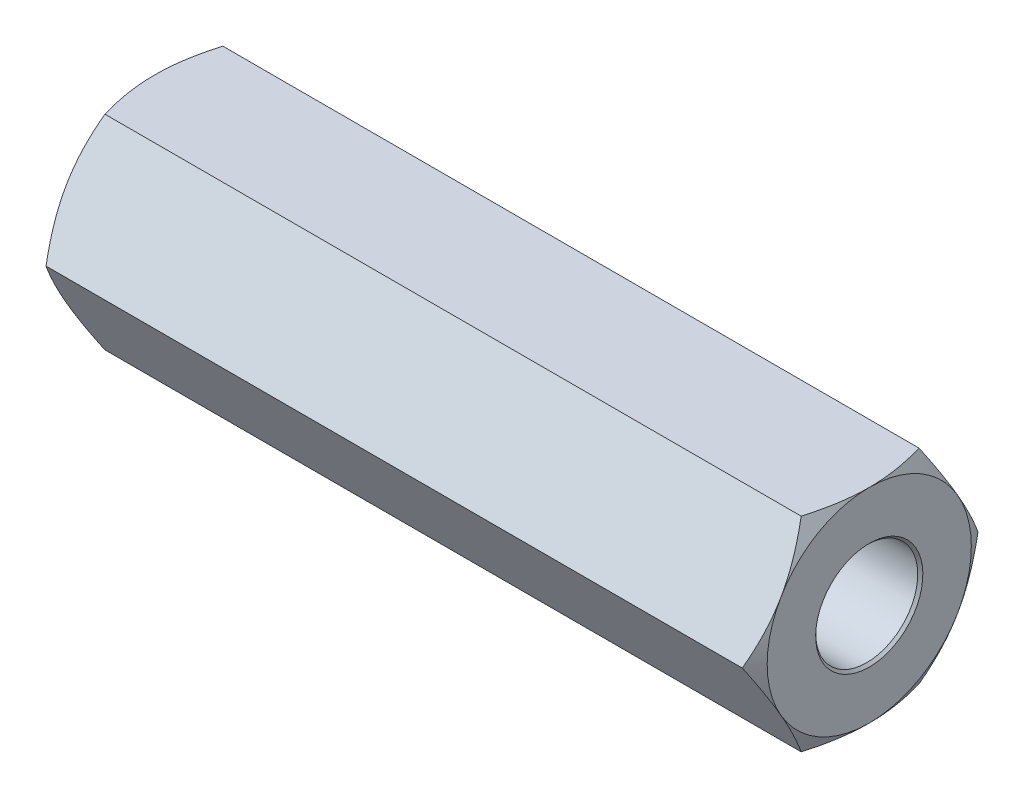
SolidWorks part; units mm, degrees
ref_plane "Front Plane" through (0, 0, 0) normal (0, 0, 1) x (1, 0, 0)
ref_plane "Top Plane" through (0, 0, 0) normal (0, 1, 0) x (1, 0, 0)
ref_plane "Right Plane" through (0, 0, 0) normal (1, 0, 0) x (0, 0, -1)
sketch "Sketch1" plane through (0, 0, 0) normal (0, 0, 1) x (1, 0, 0)
  line L0 (0, 0) -> (28, 0) construction
  line L1 (0, 4) -> (0, -4) construction
  line L2 (0, 2) -> (11.1, 2) construction
  line L3 (0, 2) -> (-0.7, 2) construction
  line L4 (0, 4) -> (28, 4) construction
  point P6 (0, 0)
  dimension "Hex" = 8
  dimension "Pitch" = 0.7
  dimension "Thread Length" = 11.1
  dimension "Thread OD" = 4
  dimension "Length" = 28
sketch "Sketch2" plane through (0, 0, 0) normal (1, 0, 0) x (0, 0, -1)
  line L0 (0, 0) -> (-1.4142, -1.4142) construction
  line L1 (2.3094, 4) -> (-2.3094, 4)
  line L2 (-2.3094, 4) -> (-4.6188, 0)
  line L3 (-4.6188, 0) -> (-2.3094, -4)
  line L4 (-2.3094, -4) -> (2.3094, -4)
  line L5 (2.3094, -4) -> (4.6188, 0)
  line L6 (4.6188, 0) -> (2.3094, 4)
  circle A0 centre (0, 0) radius 4 construction
  circle A1 centre (0, 0) radius 2 construction
  dimension "D1" = 45
extrude "Boss-Extrude1" add sketch "Sketch2" along normal up to vertex (28 mm away) up to point (28, 0, 0)
sketch "Sketch3" plane through (0, 0, 0) normal (0, 0, 1) x (1, 0, 0)
  line L0 (0, 2.1) -> (0.1, 2)
  line L1 (0, 0) -> (11.1, 0)
  line L2 (0, 0) -> (0, 2.1)
  line L3 (0.1, 2) -> (11.1, 2)
  line L4 (11.1, 0) -> (11.1, 2)
  line L5 (28, 0) -> (16.9, 0)
  line L8 (16.9, 0) -> (16.9, 2)
  line L9 (0, 4) -> (0, -4) construction
  line L13 (0, 0) -> (28, 0) construction
  line L14 (16.9, 2) -> (27.9, 2)
  line L15 (27.9, 2) -> (28, 2.1)
  line L16 (28, 4) -> (28, 0) construction
  line L17 (28, 2.1) -> (28, 0)
  dimension "D1" = 4.2
  dimension "D2" = 45
revolve "Cut-Revolve1" cut sketch "Sketch3" angle 360 about L13
sketch "Sketch4" plane through (0, 0, 0) normal (-1, 0, 0) x (0, 0, 1)
  circle A0 centre (0, 0) radius 4
  circle A1 centre (0, 0) radius 4 construction
extrude "Cut-Extrude1" cut sketch "Sketch4" against normal through all draft 60 flip side to cut
sketch "Sketch5" plane through (28, 0, 0) normal (1, 0, 0) x (0, 0, -1)
  circle A0 centre (0, 0) radius 4
  circle A1 centre (0, 0) radius 4 construction
extrude "Cut-Extrude2" cut sketch "Sketch5" against normal through all draft 60 flip side to cut
ref_axis "Center Axis 1" through (0, 0, 0) along (1, 0, 0)
sketch "Sketch6" [suppressed] plane through (0, 0, 0) normal (0, 0, 1) x (1, 0, 0)
  line L0 (-0.599, 2) -> (-0.2995, 1.4813) construction
  line L1 (-0.2995, 1.4813) -> (0, 2) construction
  line L2 (0, 2) -> (-0.599, 2) construction
  line L3 (0, 2) -> (-0.7, 2) construction
  line L5 (-0.599, 2) -> (-0.6495, 2.0875) construction
  line L6 (-0.6495, 2.0875) -> (0.0505, 2.0875) construction
  line L7 (0.0505, 2.0875) -> (0, 2) construction
  line L8 (-0.3432, 1.5571) -> (-0.2557, 1.5571) construction
  line L9 (-0.2995, 2) -> (-0.2995, 2.0875) construction
  line L10 (-0.6242, 2.0438) -> (0.0253, 2.0438)
  line L11 (0.0253, 2.0438) -> (-0.2557, 1.5571)
  line L12 (-0.2557, 1.5571) -> (-0.3432, 1.5571)
  line L13 (-0.3432, 1.5571) -> (-0.6242, 2.0438)
  dimension "D1" = 0.0875
sketch "Sketch7" [suppressed] plane through (0, 0, 0) normal (-1, 0, 0) x (0, 0, 1)
  line L0 (0, 4) -> (0, -4) construction
  circle A0 centre (0, 0) radius 2
curve "Helix/Spiral1" [suppressed] pitch 0.7 height 11.8 turns 16.8571
sweep "Sweep1" [suppressed] add profiles "Sketch6" path "Helix/Spiral1"
pattern_linear "LPattern1" [suppressed] count 2 spacing 16.9 along (1, 0, 0)
combine bodies "Combine1" [suppressed] operation type add bodies to combine 107 108 109
sketch "Sketch8" [suppressed] plane through (0, 0, 0) normal (-1, 0, 0) x (0, 0, 1)
  circle A0 centre (0, 0) radius 2.1
extrude "Cut-Extrude3" [suppressed] cut sketch "Sketch8" against normal through all draft 45 and the other way through all draft 45
sketch "Sketch9" [suppressed] plane through (28, 0, 0) normal (1, 0, 0) x (0, 0, -1)
  circle A0 centre (0, 0) radius 2.1
  circle A1 centre (0, 0) radius 2.1 construction
extrude "Cut-Extrude4" [suppressed] cut sketch "Sketch9" against normal through all draft 45 and the other way through all draft 45
equation "\"D1@Sketch3\"=\"Thread OD@Sketch1\"*1.05"
equation "\"D1@Sketch6\"=\"Pitch@Sketch1\"/8"
equation "\"D4@Helix/Spiral1\"=\"Pitch@Sketch1\""
equation "\"D3@Helix/Spiral1\"=\"Pitch@Sketch1\"+\"Thread Length@Sketch1\""
equation "\"D3@LPattern1\"=\"Length@Sketch1\"-\"Thread Length@Sketch1\""
